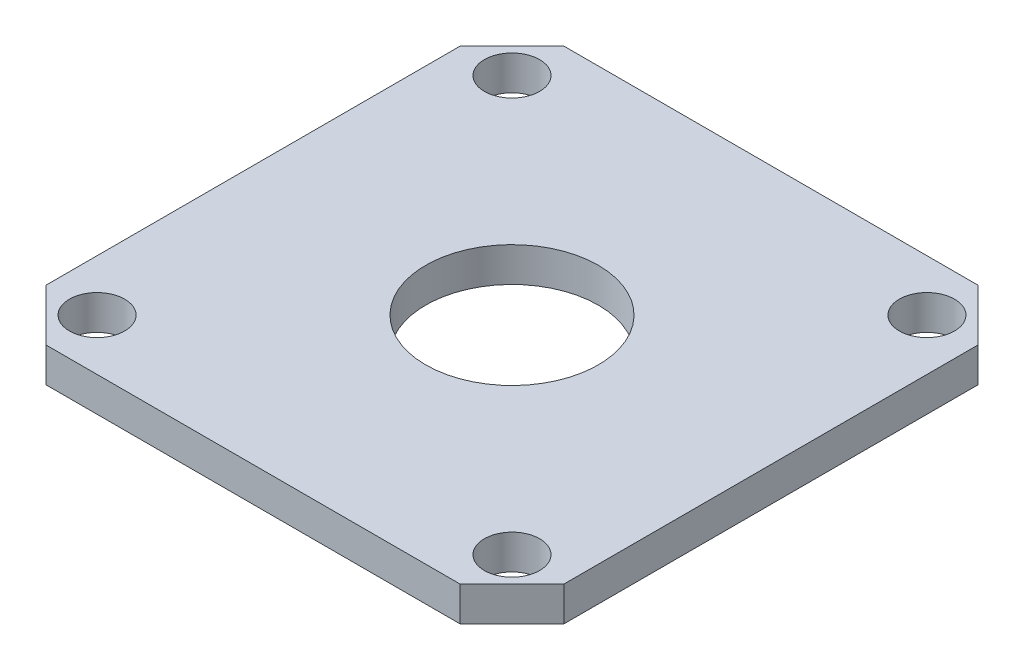
SolidWorks part; units mm, degrees
ref_plane "Front Plane" through (0, 0, 0) normal (0, 0, 1) x (1, 0, 0)
ref_plane "Top Plane" through (0, 0, 0) normal (0, 1, 0) x (1, 0, 0)
ref_plane "Right Plane" through (0, 0, 0) normal (1, 0, 0) x (0, 0, -1)
sketch "Sketch1" plane through (0, 0, 0) normal (0, 1, 0) x (1, 0, 0)
  line L0 (0, 0) -> (0, 15) construction
  line L1 (-15, 15) -> (15, 15)
  line L2 (-15, 15) -> (-15, -15)
  line L3 (-15, -15) -> (15, -15)
  line L4 (15, 15) -> (15, -15)
  line L5 (-15, 15) -> (15, -15) construction
  line L6 (-15, -15) -> (15, 15) construction
  line L7 (0, 0) -> (-15, 0) construction
  circle A0 centre (0, 0) radius 11
  circle A1 centre (0, 0) radius 5
  circle A2 centre (0, 0) radius 17 construction
  circle A3 centre (-12.0208, 12.0208) radius 1.6
  circle A4 centre (12.0208, 12.0208) radius 1.6
  circle A5 centre (-12.0208, -12.0208) radius 1.6
  circle A6 centre (12.0208, -12.0208) radius 1.6
  circle A7 centre (0, 0) radius 12
  dimension "D1" = 30
  dimension "D3" = 1
  dimension "D4" = 22
  dimension "D5" = 34
  dimension "D6" = 10
  dimension "D2" = 30
extrude "Boss-Extrude1" add sketch "Sketch1" along normal blind 2 contours L4 L1 L2 L3 A7 A6 A4 A3 A5 region at (0, 0, -14.5757)
fillet "Chamfer1" radius 3 1 edges at (15, 1, -15) type face fillet profile chamfer first side face at (15, 1, 0) second side face at (0, 1, -15)
fillet "Chamfer2" radius 3 1 edges at (-15, 1, -15) type face fillet profile chamfer first side face at (-1.5, 1, -15) second side face at (-15, 1, 0)
fillet "Chamfer3" radius 3 1 edges at (-15, 1, 15) type face fillet profile chamfer first side face at (-15, 1, 1.5) second side face at (0, 1, 15)
fillet "Chamfer4" radius 3 1 edges at (15, 1, 15) type face fillet profile chamfer first side face at (1.5, 1, 15) second side face at (15, 1, 1.5)
extrude "Boss-Extrude2" add sketch "Sketch1<6>" along normal up to surface (2 mm away) contours A0 A1 | A7 A0 region at (-10.6889, 0, 0) region at (-11.6606, 0, 0) up to face at (0, 2, 12)
sketch "Sketch1<6>" plane through (0, 0, 0) normal (0, 1, 0) x (1, 0, 0) same geometry as "Sketch1"
